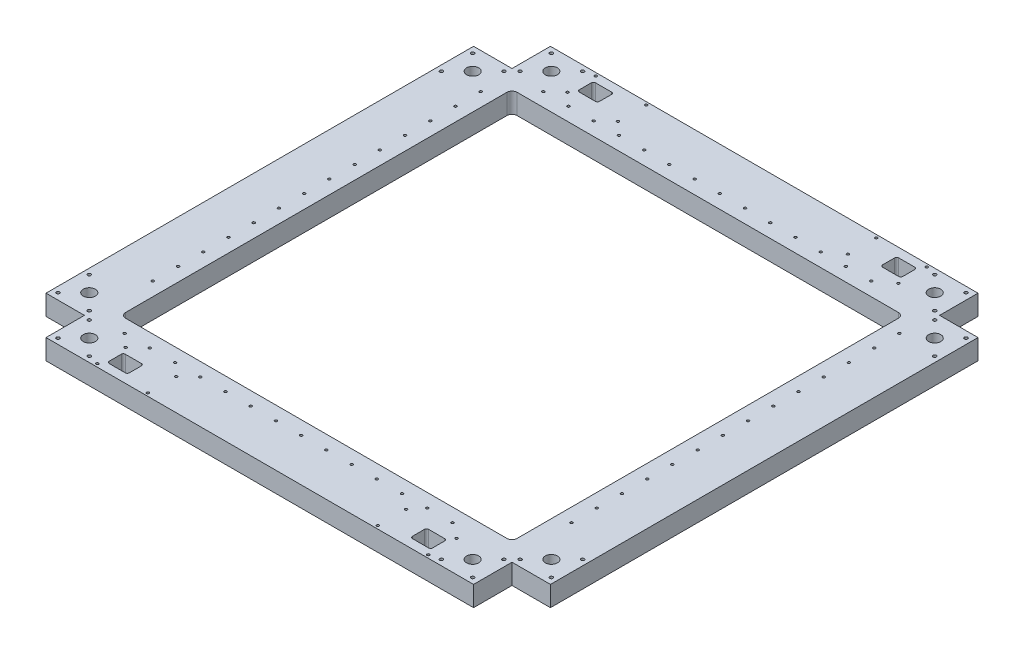
SolidWorks part; units mm, degrees
material "ASTM A36 Steel"
ref_plane "Front Plane" through (0, 0, 0) normal (0, 0, 1) x (1, 0, 0)
ref_plane "Top Plane" through (0, 0, 0) normal (0, 1, 0) x (1, 0, 0)
ref_plane "Right Plane" through (0, 0, 0) normal (1, 0, 0) x (0, 0, -1)
sketch "Sketch1" plane through (0, 0, 0) normal (0, 1, 0) x (1, 0, 0)
  line L1 (250, -250) -> (-250, -250)
  line L2 (250, -250) -> (250, 250)
  line L3 (250, 250) -> (-250, 250)
  line L4 (-250, -250) -> (-250, 250)
  line L5 (250, -250) -> (-250, 250) construction
  line L6 (250, 250) -> (-250, -250) construction
  point P0 (0, 0)
  dimension "D1" = 500
  dimension "D2" = 500
extrude "Boss-Extrude1" add sketch "Sketch1" along normal blind 20
sketch "Sketch2" plane through (0, 20, 0) normal (0, 1, 0) x (1, 0, 0)
  line L0 (250, 250) -> (-250, 250) construction
  line L10 (-250, 250) -> (-250, -250) construction
  line L15 (-250, 169) -> (-208, 169)
  line L16 (-250, 169) -> (-250, 211)
  line L17 (-174.5, 213.5) -> (-205.5, 213.5)
  line L27 (-250, 211) -> (-208, 211)
  line L33 (-208, 169) -> (-208, 211)
  line L35 (-250, 169) -> (-208, 211) construction
  line L36 (-250, 211) -> (-208, 169) construction
  line L37 (-169, 208) -> (-211, 208)
  line L38 (-169, 208) -> (-169, 250)
  line L39 (-169, 250) -> (-211, 250)
  line L40 (-211, 208) -> (-211, 250)
  line L41 (-169, 208) -> (-211, 250) construction
  line L42 (-169, 250) -> (-211, 208) construction
  line L43 (-208, 206) -> (-213, 211)
  line L44 (-174.5, 213.5) -> (-174.5, 244.5)
  line L45 (-174.5, 244.5) -> (-205.5, 244.5)
  line L46 (-205.5, 213.5) -> (-205.5, 244.5)
  line L47 (-174.5, 213.5) -> (-205.5, 244.5) construction
  line L48 (-174.5, 244.5) -> (-205.5, 213.5) construction
  line L49 (-213.5, 174.5) -> (-244.5, 174.5)
  line L50 (-213.5, 174.5) -> (-213.5, 205.5)
  line L51 (-213.5, 205.5) -> (-244.5, 205.5)
  line L52 (-244.5, 174.5) -> (-244.5, 205.5)
  line L53 (-213.5, 174.5) -> (-244.5, 205.5) construction
  line L54 (-213.5, 205.5) -> (-244.5, 174.5) construction
  line L55 (-206, 208) -> (-211, 213)
  line L56 (-213, 211) -> (-211, 213) construction
  point P1 (-229, 190)
  point P5 (-190, 229)
  point P23 (-229, 190)
  point P27 (-190, 229)
  dimension "D1" = 5
  dimension "D2" = 45
  dimension "D3" = 42
  dimension "D4" = 31
  dimension "D5" = 45
  dimension "D6" = 5
  dimension "D7" = 60
hole_wizard "Bearing Press Fit" positions "Sketch8" profile "Sketch9" hole size "Ø12.0" standard "ANSI Metric" end condition through all
sketch "Sketch8" plane through (0, 20, 0) normal (0, 1, 0) x (1, 0, 0)
  line L1 (-169, 250) -> (-211, 208) construction
  point P8 (-190, 229)
  point P12 (-229, 190)
sketch "Sketch9" plane through (-190, 20, -229) normal (1, 0, 0) x (0, 0, 1)
  line L0 (0, 0) -> (0, 20)
  line L1 (0, 20) -> (6, 20)
  line L2 (6, 20) -> (6, 0)
  line L5 (6, 0) -> (0, 0)
  line L11 (0, -6.35) -> (0, 107.95) construction
  dimension "Thru Hole Dia." = 12
  dimension "Thru Hole Depth" = 20
ref_axis "Axis1" through (0, 8.4, 0) along (0, -1, 0)
pattern_circular "CirPattern1" count 4 over 360 about axis through (0, 8.4, 0) along (0, -1, 0) of "Bearing Press Fit"
sketch "Sketch5" plane through (0, 20, 0) normal (0, 1, 0) x (1, 0, 0)
  line L1 (194, -194) -> (-194, -194)
  line L2 (194, -194) -> (194, 194)
  line L3 (194, 194) -> (-194, 194)
  line L4 (-194, -194) -> (-194, 194)
  line L5 (194, -194) -> (-194, 194) construction
  line L6 (194, 194) -> (-194, -194) construction
  point P0 (0, 0)
  dimension "D1" = 388
extrude "Cut-Extrude1" cut sketch "Sketch5" against normal up to surface (20 mm away) up to face at (-229, 0, 196)
sketch "Sketch10" plane through (0, 0, 0) normal (0, 1, 0) x (1, 0, 0)
  line L5 (194, 194) -> (-194, 194) construction
  line L6 (214, -214) -> (-214, -214)
  line L14 (214, -214) -> (214, 214)
  line L15 (214, 214) -> (-214, 214)
  line L16 (-214, -214) -> (-214, 214)
  line L17 (214, -214) -> (-214, 214) construction
  line L18 (214, 214) -> (-214, -214) construction
  line L19 (201.5, -201.5) -> (-201.5, -201.5)
  line L20 (201.5, -201.5) -> (201.5, 201.5)
  line L21 (201.5, 201.5) -> (-201.5, 201.5)
  line L22 (-201.5, -201.5) -> (-201.5, 201.5)
  line L23 (201.5, -201.5) -> (-201.5, 201.5) construction
  line L24 (201.5, 201.5) -> (-201.5, -201.5) construction
  point P0 (0, 0)
  point P6 (0, 0)
  dimension "D2" = 7.5
  dimension "D1" = 12.5
extrude "Linear Rail Slot" cut sketch "Sketch10" along normal blind 2.5
fillet "Fillet2" radius 5 4 edges at (-194, 10, 194) (194, 10, 194) (194, 10, -194) (-194, 10, -194)
sketch "Sketch11" plane through (0, 2.5, 0) normal (0, -1, 0) x (1, 0, 0)
  line L0 (-194, 207.5) -> (166, 207.5)
  line L1 (-201.5, 201.5) -> (201.5, 201.5) construction
  line L3 (-214, -214) -> (-214, 214) construction
  point P16 (148.5, 207.5)
  point P18 (123.5, 207.5)
  point P19 (98.5, 207.5)
  point P20 (73.5, 207.5)
  point P21 (48.5, 207.5)
  point P22 (23.5, 207.5)
  point P23 (-1.5, 207.5)
  point P24 (-26.5, 207.5)
  point P25 (-51.5, 207.5)
  point P26 (-76.5, 207.5)
  point P28 (-101.5, 207.5)
  point P29 (-126.5, 207.5)
  point P30 (-151.5, 207.5)
  point P31 (-176.5, 207.5)
  dimension "D1" = 360
  dimension "D2" = 6
  dimension "D4" = 14
  dimension "D5" = 25
  dimension "D6" = 20
  dimension "D3" = 17.5
hole_wizard "Tap Drill for M3x0.5 Tap1" positions "Sketch12" profile "Sketch13" hole size "M3x0.5" standard "ANSI Metric" end condition through all
sketch "Sketch12" plane through (0, 2.5, 0) normal (0, -1, 0) x (-1, 0, 0)
  line L0 (194, -207.5) -> (-166, -207.5) construction
  point P28 (-148.5, -207.5)
  point P31 (-123.5, -207.5)
  point P34 (-98.5, -207.5)
  point P37 (-73.5, -207.5)
  point P40 (-48.5, -207.5)
  point P43 (-23.5, -207.5)
  point P46 (1.5, -207.5)
  point P49 (26.5, -207.5)
  point P51 (51.5, -207.5)
  point P54 (76.5, -207.5)
  point P57 (101.5, -207.5)
  point P61 (126.5, -207.5)
  point P64 (151.5, -207.5)
  point P67 (176.5, -207.5)
sketch "Sketch13" plane through (148.5, 2.5, 207.5) normal (1, 0, 0) x (0, 0, -1)
  line L0 (0, 0) -> (0, 17.5)
  line L1 (0, 17.5) -> (1.25, 17.5)
  line L2 (1.25, 17.5) -> (1.25, 0)
  line L5 (1.25, 0) -> (0, 0)
  line L11 (0, -6.35) -> (0, 107.95) construction
  dimension "Thru Hole Dia." = 2.5
  dimension "Thru Hole Depth" = 17.5
sketch "Sketch14" plane through (0, 0, 0) normal (0, -1, 0) x (1, 0, 0)
  line L1 (-151.5, 213.5) -> (-176.5, 213.5)
  line L2 (-147.5, 217.5) -> (-147.5, 219.5)
  line L3 (-151.5, 223.5) -> (-176.5, 223.5)
  line L4 (-180.5, 217.5) -> (-180.5, 219.5)
  line L5 (-147.5, 213.5) -> (-180.5, 223.5) construction
  line L6 (-147.5, 223.5) -> (-180.5, 213.5) construction
  line L7 (-201.5, 201.5) -> (201.5, 201.5) construction
  line L8 (-176.5, 207.5) -> (-151.5, 207.5) construction
  line L19 (-1.5, 213.5) -> (-26.5, 213.5)
  line L25 (2.5, 217.5) -> (2.5, 219.5)
  line L26 (-1.5, 223.5) -> (-26.5, 223.5)
  line L31 (-30.5, 217.5) -> (-30.5, 219.5)
  line L32 (2.5, 213.5) -> (-30.5, 223.5) construction
  line L33 (2.5, 223.5) -> (-30.5, 213.5) construction
  line L34 (-26.5, 207.5) -> (-1.5, 207.5) construction
  line L35 (148.5, 213.5) -> (123.5, 213.5)
  line L36 (152.5, 217.5) -> (152.5, 219.5)
  line L37 (148.5, 223.5) -> (123.5, 223.5)
  line L38 (119.5, 217.5) -> (119.5, 219.5)
  line L39 (152.5, 213.5) -> (119.5, 223.5) construction
  line L40 (152.5, 223.5) -> (119.5, 213.5) construction
  line L41 (123.5, 207.5) -> (148.5, 207.5) construction
  arc A3 (-147.5, 219.5) -> (-151.5, 223.5) centre (-151.5, 219.5) ccw
  arc A4 (-151.5, 213.5) -> (-147.5, 217.5) centre (-151.5, 217.5) ccw
  arc A5 (-176.5, 213.5) -> (-180.5, 217.5) centre (-176.5, 217.5) cw
  arc A6 (-176.5, 223.5) -> (-180.5, 219.5) centre (-176.5, 219.5) ccw
  arc A7 (2.5, 219.5) -> (-1.5, 223.5) centre (-1.5, 219.5) ccw
  arc A8 (-1.5, 213.5) -> (2.5, 217.5) centre (-1.5, 217.5) ccw
  arc A9 (-26.5, 213.5) -> (-30.5, 217.5) centre (-26.5, 217.5) cw
  arc A10 (-26.5, 223.5) -> (-30.5, 219.5) centre (-26.5, 219.5) ccw
  arc A11 (152.5, 219.5) -> (148.5, 223.5) centre (148.5, 219.5) ccw
  arc A12 (148.5, 213.5) -> (152.5, 217.5) centre (148.5, 217.5) ccw
  arc A13 (123.5, 213.5) -> (119.5, 217.5) centre (123.5, 217.5) cw
  arc A14 (123.5, 223.5) -> (119.5, 219.5) centre (123.5, 219.5) ccw
  point P0 (-164, 218.5)
  point P12 (-164, 207.5)
  point P26 (-14, 218.5)
  point P45 (136, 218.5)
  dimension "D5" = 3
  dimension "D4" = 4
  dimension "D1" = 33
  dimension "D2" = 12
  dimension "D3" = 10
  dimension "D7" = 25
  dimension "D6" = 150
mirror "Mirror5" about plane through (0, 0, 0) normal (0, 0, 1) of "Tap Drill for M3x0.5 Tap1"
ref_plane "Plane1" through (0, 0, 0) normal (-0.7071, 0, 0.7071) x (0.7071, 0, 0.7071)
mirror "Mirror6" about plane through (0, 0, 0) normal (-0.7071, 0, 0.7071) of "Mirror5"
sketch "Sketch19" plane through (0, 2.5, 0) normal (0, -1, 0) x (1, 0, 0)
  line L0 (-198.5, 201.5) -> (-198.5, 214)
  line L1 (-201.5, 201.5) -> (201.5, 201.5) construction
  line L2 (-214, 214) -> (214, 214) construction
  line L3 (-198.5, 214) -> (-214, 214)
  line L4 (-214, 214) -> (-214, 198.5)
  line L5 (-214, -214) -> (-214, 214) construction
  line L6 (-214, 198.5) -> (-201.5, 198.5)
  line L7 (-201.5, -201.5) -> (-201.5, 201.5) construction
  line L8 (-201.5, 198.5) -> (-201.5, 201.5)
  line L9 (-201.5, 201.5) -> (-198.5, 201.5)
  dimension "D1" = 3
extrude "Boss-Extrude2" add sketch "Sketch19" along normal up to surface (2.5 mm away) up to face at (-229, 0, 196)
pattern_circular "CirPattern4" count 4 over 360 about axis through (0, 8.4, 0) along (0, -1, 0) of "Boss-Extrude2"
sketch "Sketch20" plane through (0, 20, 0) normal (0, 1, 0) x (1, 0, 0)
  line L5 (-250, -250) -> (250, -250) construction
  line L20 (140.3, -225) -> (160.3, -241) construction
  line L23 (160.3, -225) -> (140.3, -241) construction
  line L28 (114, -247) -> (164, -219) construction
  line L29 (164, -247) -> (114, -219) construction
  line L30 (164, -219) -> (114, -219) construction
  line L31 (114, -247) -> (114, -219) construction
  line L32 (164, -247) -> (114, -247) construction
  line L33 (164, -247) -> (164, -219) construction
  line L34 (158.3, -241) -> (142.3, -241)
  line L35 (140.3, -227) -> (140.3, -239)
  line L36 (158.3, -225) -> (142.3, -225)
  line L37 (160.3, -227) -> (160.3, -239)
  arc A12 (142.3, -225) -> (140.3, -227) centre (142.3, -227) ccw
  arc A13 (140.3, -239) -> (142.3, -241) centre (142.3, -239) ccw
  arc A14 (160.3, -239) -> (158.3, -241) centre (158.3, -239) cw
  arc A15 (160.3, -227) -> (158.3, -225) centre (158.3, -227) ccw
  circle A16 centre (190, -229) radius 6 construction
  point P65 (150.3, -233)
  point P66 (139, -233)
  point P67 (139, -233)
  dimension "D7" = 39.7
  dimension "D8" = 11.3
  dimension "D6" = 2
  dimension "D1" = 28
  dimension "D2" = 50
  dimension "D3" = 17
  dimension "D4" = 20
  dimension "D5" = 16
extrude "Cut-Extrude3" cut sketch "Sketch20" against normal through all
hole_wizard "Tap Drill for M3x0.5 Tap3" positions "Sketch28" profile "Sketch29" hole size "M3x0.5" standard "ANSI Metric" end condition through all
sketch "Sketch28" plane through (0, 20, 0) normal (0, 1, 0) x (1, 0, 0)
  point P0 (164, -219)
  point P3 (164, -247)
  point P6 (114, -247)
  point P8 (114, -219)
sketch "Sketch29" plane through (164, 20, 219) normal (1, 0, 0) x (0, 0, 1)
  line L0 (0, 0) -> (0, 20)
  line L1 (0, 20) -> (1.25, 20)
  line L2 (1.25, 20) -> (1.25, 0)
  line L5 (1.25, 0) -> (0, 0)
  line L11 (0, -6.35) -> (0, 107.95) construction
  dimension "Thru Hole Dia." = 2.5
  dimension "Thru Hole Depth" = 20
mirror "Mirror8" about plane through (0, 0, 0) normal (1, 0, 0) of "Tap Drill for M3x0.5 Tap3", "Cut-Extrude3"
mirror "Mirror9" about plane through (0, 0, 0) normal (0, 0, 1) of "Mirror8"
sketch "Sketch24" plane through (0, 20, 0) normal (0, 1, 0) x (1, 0, 0)
  line L1 (244.5, -205.5) -> (213.5, -205.5)
  line L2 (244.5, -205.5) -> (244.5, -174.5)
  line L3 (244.5, -174.5) -> (213.5, -174.5)
  line L4 (213.5, -205.5) -> (213.5, -174.5)
  line L5 (244.5, -205.5) -> (213.5, -174.5) construction
  line L6 (244.5, -174.5) -> (213.5, -205.5) construction
  line L7 (205.5, -244.5) -> (174.5, -244.5)
  line L8 (205.5, -244.5) -> (205.5, -213.5)
  line L9 (205.5, -213.5) -> (174.5, -213.5)
  line L10 (174.5, -244.5) -> (174.5, -213.5)
  line L11 (205.5, -244.5) -> (174.5, -213.5) construction
  line L12 (205.5, -213.5) -> (174.5, -244.5) construction
  point P0 (229, -190)
  point P6 (190, -229)
  dimension "D1" = 31
hole_wizard "M3 Clearance Hole1" positions "Sketch25" profile "Sketch26" hole size "M3" standard "ANSI Metric" end condition through all
sketch "Sketch25" plane through (0, 20, 0) normal (0, 1, 0) x (1, 0, 0)
  point P0 (205.5, -244.5)
  point P3 (205.5, -213.5)
  point P9 (174.5, -244.5)
  point P12 (213.5, -205.5)
  point P18 (244.5, -174.5)
  point P21 (244.5, -205.5)
sketch "Sketch26" plane through (205.5, 20, 244.5) normal (1, 0, 0) x (0, 0, 1)
  line L0 (0, 0) -> (0, 20)
  line L1 (0, 20) -> (1.6, 20)
  line L2 (1.6, 20) -> (1.6, 0)
  line L5 (1.6, 0) -> (0, 0)
  line L11 (0, -6.35) -> (0, 107.95) construction
  dimension "Thru Hole Dia." = 3.2
  dimension "Thru Hole Depth" = 20
sketch "Sketch27" plane through (0, 20, 0) normal (0, 1, 0) x (1, 0, 0)
  line L1 (250, -250) -> (211.9, -250)
  line L2 (250, -250) -> (250, -211.9)
  line L3 (250, -211.9) -> (211.9, -211.9)
  line L4 (211.9, -250) -> (211.9, -211.9)
  dimension "D1" = 38.1
extrude "Cut-Extrude4" cut sketch "Sketch27" against normal up to surface (20 mm away) up to face at (205.5, 0, 246.1)
pattern_circular "CirPattern3" count 4 over 360 about axis through (0, 8.4, 0) along (0, -1, 0) of "M3 Clearance Hole1", "Cut-Extrude4"
fillet "Fillet5" radius 4 16 edges at (198.5, 1.25, 214) (198.5, 1.25, 201.5) (201.5, 1.25, 198.5) (214, 1.25, 198.5) (-214, 1.25, 198.5) (-198.5, 1.25, 214) (-201.5, 1.25, 198.5) (-198.5, 1.25, 201.5) (-214, 1.25, -198.5) (-198.5, 1.25, -214) (-198.5, 1.25, -201.5) (-201.5, 1.25, -198.5) (198.5, 1.25, -201.5) (198.5, 1.25, -214) (201.5, 1.25, -198.5) (214, 1.25, -198.5)
